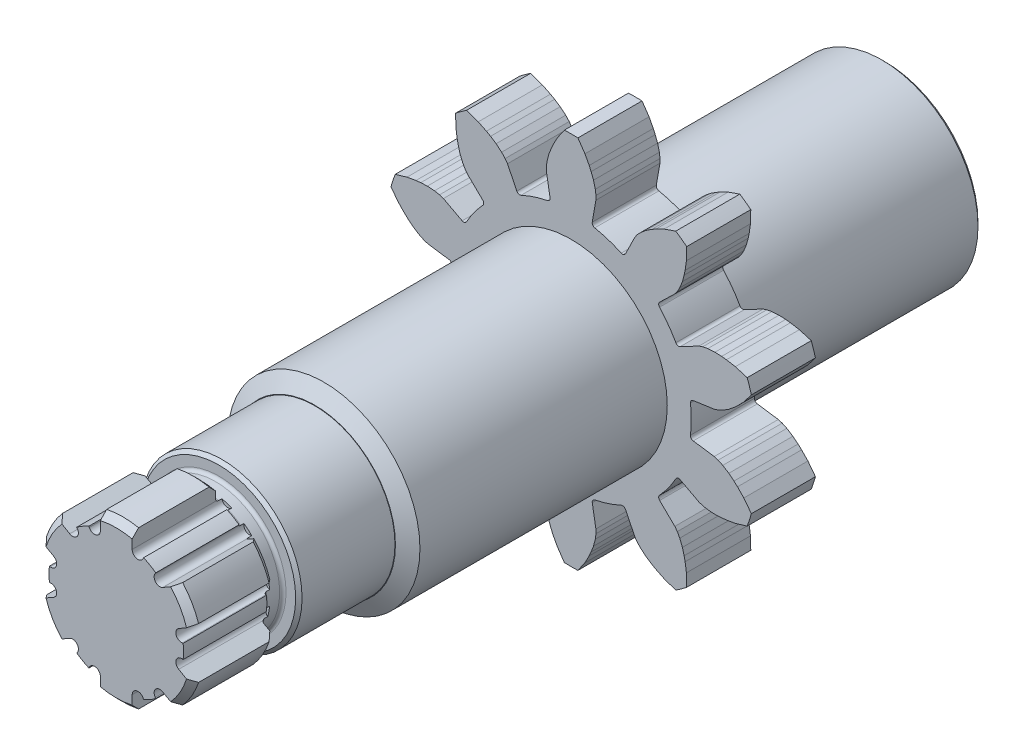
SolidWorks part; units mm, degrees
note: '?' marks a value the reader was unsure of.
material "PW70:3:C1:0:1:2:Re:26:"
ref_plane "Plan1" through (0, 0, 0) normal (0, 0, 1) x (1, 0, 0)
ref_plane "Plan2" through (0, 0, 0) normal (0, 1, 0) x (1, 0, 0)
ref_plane "Plan3" through (0, 0, 0) normal (1, 0, 0) x (0, 0, -1)
sketch "Esquisse1" plane through (0, 0, 0) normal (0, 0, 1) x (1, 0, 0)
  circle A0 centre (0, 0) radius 29.25
  dimension "D1" = 58.5
extrude "Base-Extrusion" add sketch "Esquisse1" along normal blind 10
sketch "Esquisse2" plane through (0, 0, 10) normal (0, 0, 1) x (1, 0, 0)
  line L0 (1.0549, 29.231) -> (2.154, 27.6377)
  line L1 (2.154, 27.6377) -> (2.8137, 26.3859)
  line L2 (2.9743, 26.0813) -> (2.154, 27.6377) construction
  line L3 (2.8137, 26.3859) -> (3.119, 25.7041)
  line L4 (3.4898, 24.7374) -> (2.9743, 26.0813) construction
  line L5 (3.119, 25.7041) -> (3.4898, 24.7374)
  line L6 (3.4898, 24.7374) -> (3.6272, 24.1947)
  line L7 (3.7645, 23.652) -> (3.4898, 24.7374) construction
  line L8 (3.6272, 24.1947) -> (3.7645, 23.652)
  line L9 (3.7645, 23.652) -> (3.868, 22.859)
  line L10 (3.868, 22.859) -> (3.8596, 22.2199)
  line L11 (3.8596, 22.2199) -> (3.7076, 21.3447)
  line L12 (3.8596, 22.2199) -> (3.1815, 18.3161) construction
  line L13 (3.7076, 21.3447) -> (3.2933, 18.9596)
  line L14 (0, 0) -> (0, 30) construction
  line L15 (0, 0) -> (9.631, 29.6412) construction
  line L16 (9.5466, 19.4474) -> (8.4799, 17.2744)
  line L17 (9.9381, 20.2449) -> (9.5466, 19.4474)
  line L18 (10.3069, 20.7669) -> (9.9381, 20.2449)
  line L19 (10.8568, 21.3475) -> (10.3069, 20.7669)
  line L20 (11.2868, 21.7059) -> (10.8568, 21.3475)
  line L21 (11.7169, 22.0642) -> (11.2868, 21.7059)
  line L22 (12.5852, 22.6283) -> (11.7169, 22.0642)
  line L23 (13.2329, 23.0005) -> (12.5852, 22.6283)
  line L24 (14.5025, 23.6255) -> (13.2329, 23.0005)
  line L25 (16.3281, 24.2684) -> (14.5025, 23.6255)
  arc A0 (16.3281, 24.2684) -> (1.0549, 29.231) centre (0, 0) ccw
  arc A1 (7.8224, 17.0403) -> (3.6876, 18.3838) centre (0, 0) ccw
  arc A2 (3.6876, 18.3838) -> (3.2933, 18.9596) centre (3.7859, 18.874) cw
  arc A3 (7.8224, 17.0403) -> (8.4799, 17.2744) centre (8.031, 17.4947) ccw
  dimension "D1" = 37.5
  dimension "D3" = 0.5
  dimension "D2" = 18
extrude "Enlèv. mat.-Extru.1" cut sketch "Esquisse2" against normal through all
ref_axis "Axe1" through (0, 0, -50) along (0, 0, 1)?
ref_axis "Axe3" through (0, 50, 0) along (0, -1, 0)?
pattern_circular "Répétition circulaire1" count 10 over 360 about axis through (0, 0, 0) along (0, 0, 1) of "Enlèv. mat.-Extru.1"
sketch "Esquisse3" plane through (0, 0, 10) normal (0, 0, 1) x (1, 0, 0)
  circle A0 centre (0, 0) radius 15
  dimension "D1" = 30
extrude "Boss.-Extru.1" add sketch "Esquisse3" along normal blind 40 and the other way blind 49
sketch "Esquisse4" plane through (0, 0, 50) normal (0, 0, 1) x (1, 0, 0)
  circle A0 centre (0, 0) radius 12.5
  dimension "D1" = 25
extrude "Boss.-Extru.2" add sketch "Esquisse4" along normal blind 31
ref_plane "Plan4" through (0, 0, 68) normal (0, 0, 1) x (1, 0, 0)
sketch "Esquisse5" plane through (0, 0, 68) normal (0, 0, 1) x (1, 0, 0)
  circle A0 centre (0, 0) radius 10
  dimension "D1" = 20
extrude "Enlèv. mat.-Extru.2" cut sketch "Esquisse5" against normal blind 3 flip side to cut
chamfer "Chanfrein1" distance 0.5 angle 45 2 edges at (15, 0, -39) (12.5, 0, 65)
chamfer "Chanfrein2" distance 1 angle 45 2 edges at (12.5, 0, 81) (12.5, 0, 68)
chamfer "Chanfrein3" distance 1.4 angle 60 1 edges at (15, 0, 50)
fillet "Congé2" radius 0.5 2 edges at (10, 0, 65) (10, 0, 68)
sketch "Esquisse6" plane through (0, 0, 81) normal (0, 0, 1) x (1, 0, 0)
  line L15 (2.4824, 12.7599) -> (2.4824, 9.8186)
  line L16 (9.8033, 8.5332) -> (7.2561, 7.0625)
  line L17 (6.1678, 8.4945) -> (6.078, 8.3709)
  line L18 (4.2668, 9.5921) -> (4.2046, 9.4525)
  line L19 (5.246, 9.0931) -> (-0.004, -0.0001) construction
  arc A12 (6.1678, 8.4945) -> (4.2668, 9.5921) centre (-0.004, -0.0001) ccw
  arc A13 (9.8033, 8.5332) -> (2.4824, 12.7599) centre (-0.004, -0.0001) ccw
  arc A14 (4.2046, 9.4525) -> (2.4824, 9.8186) centre (3.3824, 9.8186) cw
  arc A15 (6.078, 8.3709) -> (7.2561, 7.0625) centre (6.8061, 7.8419) ccw
extrude "Enlèv. mat.-Extru.3" cut sketch "Esquisse6" against normal blind 14
pattern_circular "Répétition circulaire2" count 6 over 360 about axis through (0, 0, 0) along (0, 0, 1) of "Enlèv. mat.-Extru.3"
